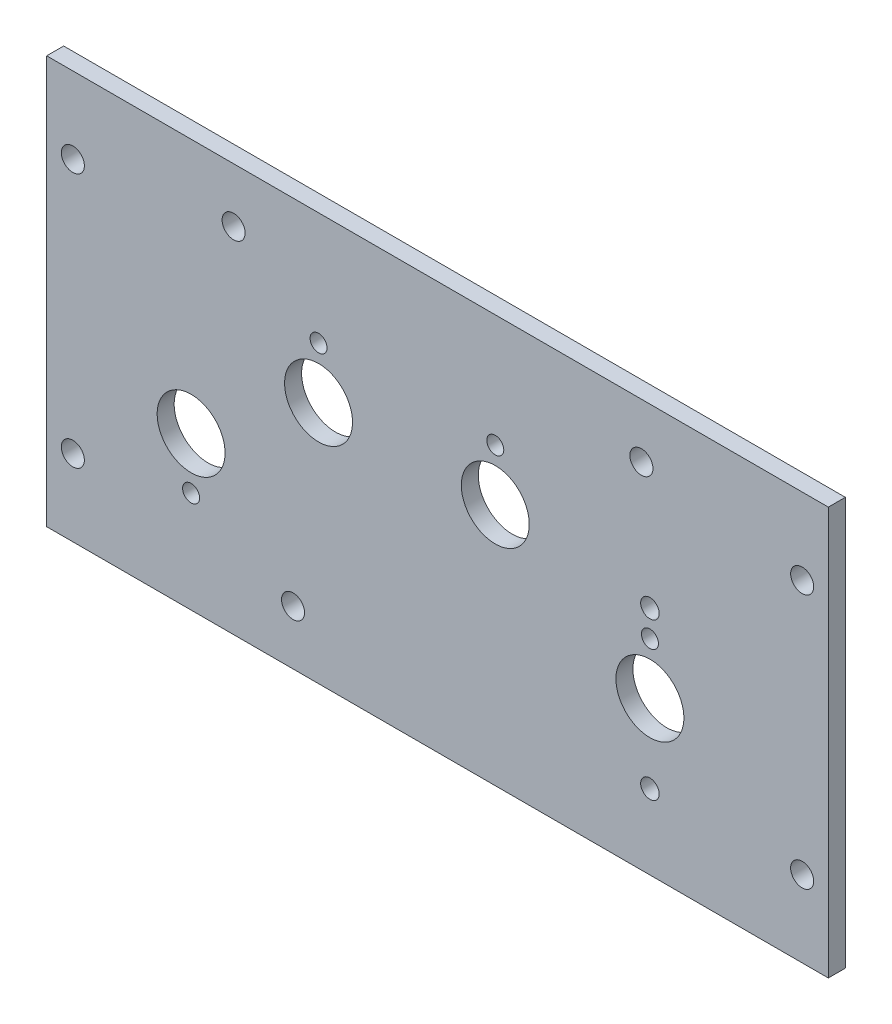
SolidWorks part; units mm, degrees
ref_plane "Front Plane" through (0, 0, 0) normal (0, 0, 1) x (1, 0, 0)
ref_plane "Top Plane" through (0, 0, 0) normal (0, 1, 0) x (1, 0, 0)
ref_plane "Right Plane" through (0, 0, 0) normal (1, 0, 0) x (0, 0, -1)
sketch "Sketch1" plane through (0, 0, 0) normal (0, 0, 1) x (1, 0, 0)
  line L4 (0, 76.2) -> (-146.05, 76.2)
  line L5 (-146.05, 76.2) -> (-146.05, 0)
  line L6 (-146.05, 0) -> (0, 0)
  line L7 (0, 0) -> (0, 76.2)
  line L8 (0, 76.2) -> (-146.05, 76.2)
  line L9 (-146.05, 76.2) -> (-146.05, 0)
  line L10 (-146.05, 0) -> (0, 0)
  line L11 (0, 0) -> (0, 76.2)
  dimension "D1" = 0
extrude "Boss-Extrude1" add sketch "Sketch1" against normal blind 3.175
hole_wizard "1/8 (0.125) Diameter Hole1" positions "Sketch3" profile "Sketch2" hole size "1/8" standard "ANSI Inch" end condition through all
sketch "Sketch3" plane through (0, 0, -3.175) normal (0, 0, -1) x (-1, 0, 0)
  circle A0 centre (95.25, 45.466) radius 9.652 construction
  circle A1 centre (119.0625, 28.575) radius 9.652 construction
  circle A2 centre (62.23, 45.466) radius 9.652 construction
  circle A3 centre (33.3375, 28.575) radius 9.652 construction
  point P0 (95.25, 55.118)
  point P4 (119.0625, 18.923)
  point P8 (62.23, 55.118)
  point P12 (33.3375, 38.227)
sketch "Sketch2" plane through (-95.25, 55.118, -3.175) normal (1, 0, 0) x (0, 1, 0)
  line L0 (0, 0) -> (0, 3.175)
  line L1 (0, 3.175) -> (1.5875, 3.175)
  line L2 (1.5875, 3.175) -> (1.5875, 0)
  line L5 (1.5875, 0) -> (0, 0)
  line L11 (0, -6.35) -> (0, 107.95) construction
  dimension "Thru Hole Dia." = 3.175
  dimension "Thru Hole Depth" = 3.175
hole_wizard "1/2 (0.5) Diameter Hole1" positions "Sketch5" profile "Sketch4" hole size "1/2" standard "ANSI Inch" end condition through all
sketch "Sketch5" plane through (0, 0, -3.175) normal (0, 0, -1) x (-1, 0, 0)
  point P0 (95.25, 45.466)
  point P3 (119.0625, 28.575)
  point P6 (62.23, 45.466)
  point P9 (33.3375, 28.575)
sketch "Sketch4" plane through (-95.25, 45.466, -3.175) normal (1, 0, 0) x (0, 1, 0)
  line L0 (0, 0) -> (0, 3.175)
  line L1 (0, 3.175) -> (6.35, 3.175)
  line L2 (6.35, 3.175) -> (6.35, 0)
  line L5 (6.35, 0) -> (0, 0)
  line L11 (0, -6.35) -> (0, 107.95) construction
  dimension "Thru Hole Dia." = 12.7
  dimension "Thru Hole Depth" = 3.175
hole_wizard "#6 Clearance Hole1" positions "Sketch7" profile "Sketch6" hole size "#6" standard "ANSI Inch" end condition through all
sketch "Sketch7" plane through (0, 0, -3.175) normal (0, 0, -1) x (-1, 0, 0)
  point P0 (141.1605, 61.9125)
  point P3 (141.1605, 14.2875)
  point P6 (4.8895, 61.9125)
  point P10 (4.8895, 14.2875)
  point P13 (111.125, 66.04)
  point P16 (100.015, 10.16)
  point P19 (34.925, 66.04)
sketch "Sketch6" plane through (-141.1605, 61.9125, -3.175) normal (1, 0, 0) x (0, 1, 0)
  line L0 (0, 0) -> (0, 3.175)
  line L1 (0, 3.175) -> (2.1526, 3.175)
  line L2 (2.1526, 3.175) -> (2.1526, 0)
  line L5 (2.1526, 0) -> (0, 0)
  line L11 (0, -6.35) -> (0, 107.95) construction
  dimension "Thru Hole Dia." = 4.3053
  dimension "Thru Hole Depth" = 3.175
hole_wizard "#4 Clearance Hole1" positions "Sketch9" profile "Sketch8" hole size "#4" standard "ANSI Inch" end condition through all
sketch "Sketch9" plane through (0, 0, -3.175) normal (0, 0, -1) x (-1, 0, 0)
  point P0 (33.3375, 43.18)
  point P3 (33.3375, 13.97)
sketch "Sketch8" plane through (-33.3375, 43.18, -3.175) normal (1, 0, 0) x (0, 1, 0)
  line L0 (0, 0) -> (0, 3.175)
  line L1 (0, 3.175) -> (1.7272, 3.175)
  line L2 (1.7272, 3.175) -> (1.7272, 0)
  line L5 (1.7272, 0) -> (0, 0)
  line L11 (0, -6.35) -> (0, 107.95) construction
  dimension "Thru Hole Dia." = 3.4544
  dimension "Thru Hole Depth" = 3.175
